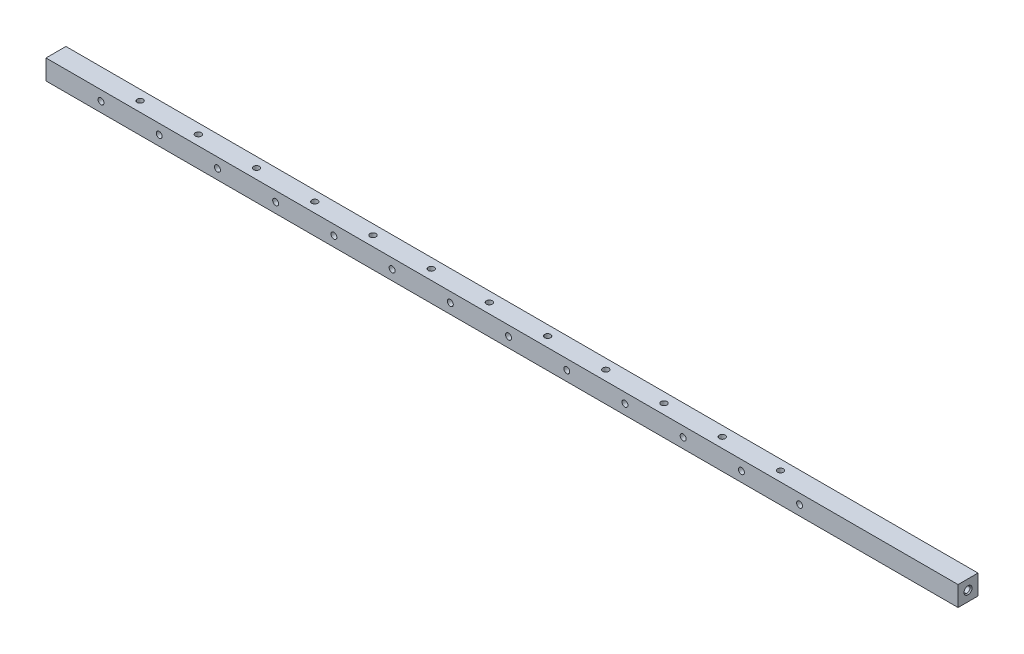
SolidWorks part; units mm, degrees
material "6061 Alloy"
ref_plane "Front Plane" through (0, 0, 0) normal (0, 0, 1) x (1, 0, 0)
ref_plane "Top Plane" through (0, 0, 0) normal (0, 1, 0) x (1, 0, 0)
ref_plane "Right Plane" through (0, 0, 0) normal (1, 0, 0) x (0, 0, -1)
sketch "Sketch1" plane through (0, 0, 0) normal (1, 0, 0) x (0, 0, -1)
  line L1 (6.35, -6.35) -> (-6.35, -6.35)
  line L2 (6.35, -6.35) -> (6.35, 6.35)
  line L3 (6.35, 6.35) -> (-6.35, 6.35)
  line L4 (-6.35, -6.35) -> (-6.35, 6.35)
  line L5 (6.35, -6.35) -> (-6.35, 6.35) construction
  line L6 (6.35, 6.35) -> (-6.35, -6.35) construction
  point P0 (0, 0)
  dimension "D1" = 12.7
  dimension "D2" = 12.7
extrude "Boss-Extrude1" add sketch "Sketch1" along normal blind 581
sketch "Sketch2" plane through (0, 0, 0) normal (-1, 0, 0) x (0, 0, 1)
  circle A0 centre (0, 0) radius 4.7625
  dimension "D1" = 9.525
sketch "Sketch9" plane through (581, 0, 0) normal (1, 0, 0) x (0, 0, -1)
  circle A0 centre (0, 0) radius 4.7625
  dimension "D1" = 9.525
hole_wizard "#10-24 Tapped Hole1" positions "Sketch12" profile "Sketch13" tap size "#10-24" standard "ANSI Inch" end condition through all
sketch "Sketch12" plane through (0, 0, 6.35) normal (0, 0, 1) x (1, 0, 0)
  line L0 (0, 6.35) -> (0, -6.35) construction
  point P0 (35.052, 0)
  dimension "D1" = 35.052
sketch "Sketch13" plane through (35.052, 0, 6.35) normal (1, 0, 0) x (0, -1, 0)
  line L0 (0, 0) -> (0, 12.7)
  line L1 (0, 12.7) -> (1.8986, 12.7)
  line L2 (1.8986, 12.7) -> (1.8986, 0)
  line L5 (1.8986, 0) -> (0, 0)
  line L11 (0, -6.35) -> (0, 107.95) construction
  dimension "Thru Tap Drill Dia." = 3.7973
  dimension "Thru Tap Drill Depth" = 12.7
cosmetic thread "Hole Thread1" parameters "D2"=4.826
hole_wizard "#10-24 Tapped Hole2" positions "Sketch14" profile "Sketch15" tap size "#10-24" standard "ANSI Inch" end condition through all
sketch "Sketch14" plane through (0, 6.35, 0) normal (0, 1, 0) x (1, 0, 0)
  line L0 (0, 6.35) -> (0, -6.35) construction
  point P0 (53.594, 0)
  dimension "D1" = 53.594
sketch "Sketch15" plane through (53.594, 6.35, 0) normal (1, 0, 0) x (0, 0, 1)
  line L0 (0, 0) -> (0, 12.7)
  line L1 (0, 12.7) -> (1.8986, 12.7)
  line L2 (1.8986, 12.7) -> (1.8986, 0)
  line L5 (1.8986, 0) -> (0, 0)
  line L11 (0, -6.35) -> (0, 107.95) construction
  dimension "Thru Tap Drill Dia." = 3.7973
  dimension "Thru Tap Drill Depth" = 12.7
cosmetic thread "Hole Thread2" parameters "D2"=4.826
hole_wizard "M6x1.0 Tapped Hole2" positions "Sketch18" profile "Sketch19" tap size "M6x1.0" standard "ANSI Metric"
sketch "Sketch18" plane through (0, 0, 0) normal (-1, 0, 0) x (0, 0, 1)
  point P0 (0, 0)
sketch "Sketch19" plane through (0, 0, 0) normal (0, 1, 0) x (0, 0, 1)
  line L0 (0, 0) -> (0, 21.8222)
  line L1 (0, 21.8222) -> (2.5, 20.32)
  line L2 (2.5, 20.32) -> (2.5, 0.525)
  line L3 (2.5, 0.525) -> (3.025, 0)
  line L5 (3.025, 0) -> (0, 0)
  line L6 (-2.5, 0.525) -> (-3.025, 0) construction
  line L10 (0, 21.8222) -> (-2.5, 20.32) construction
  line L11 (0, -6.35) -> (0, 107.95) construction
  dimension "Tap Drill Dia." = 5
  dimension "Tap Drill Depth" = 20.32
  dimension "Near C'Sink Dia." = 6.05
  dimension "Near C'Sink Angle" = 90
  dimension "Drill Angle" = 118
cosmetic thread "Hole Thread6" parameters "D1"=15.24, "D2"=6
hole_wizard "#10-24 Tapped Hole3" positions "Sketch20" profile "Sketch21" tap size "#10-24" standard "ANSI Inch"
sketch "Sketch20" plane through (581, 0, 0) normal (1, 0, 0) x (0, 0, -1)
  point P0 (0, 0)
sketch "Sketch21" plane through (581, 0, 0) normal (0, 1, 0) x (0, 0, -1)
  line L0 (0, 0) -> (0, 21.7148)
  line L1 (0, 21.7148) -> (1.8986, 20.574)
  line L2 (1.8986, 20.574) -> (1.8986, 0.635)
  line L3 (1.8986, 0.635) -> (2.5337, 0)
  line L5 (2.5337, 0) -> (0, 0)
  line L6 (-1.8986, 0.635) -> (-2.5337, 0) construction
  line L10 (0, 21.7148) -> (-1.8987, 20.574) construction
  line L11 (0, -6.35) -> (0, 107.95) construction
  dimension "Tap Drill Dia." = 3.7973
  dimension "Tap Drill Depth" = 20.574
  dimension "Near C'Sink Dia." = 5.0673
  dimension "Near C'Sink Angle" = 90
  dimension "Drill Angle" = 118
cosmetic thread "Hole Thread9" parameters "D1"=15.24, "D2"=6
pattern_linear "LPattern1" count 13 spacing 37.084 along (1, 0, 0) of "#10-24 Tapped Hole1"
pattern_linear "LPattern2" count 12 spacing 37.084 along (1, 0, 0) of "#10-24 Tapped Hole2"
